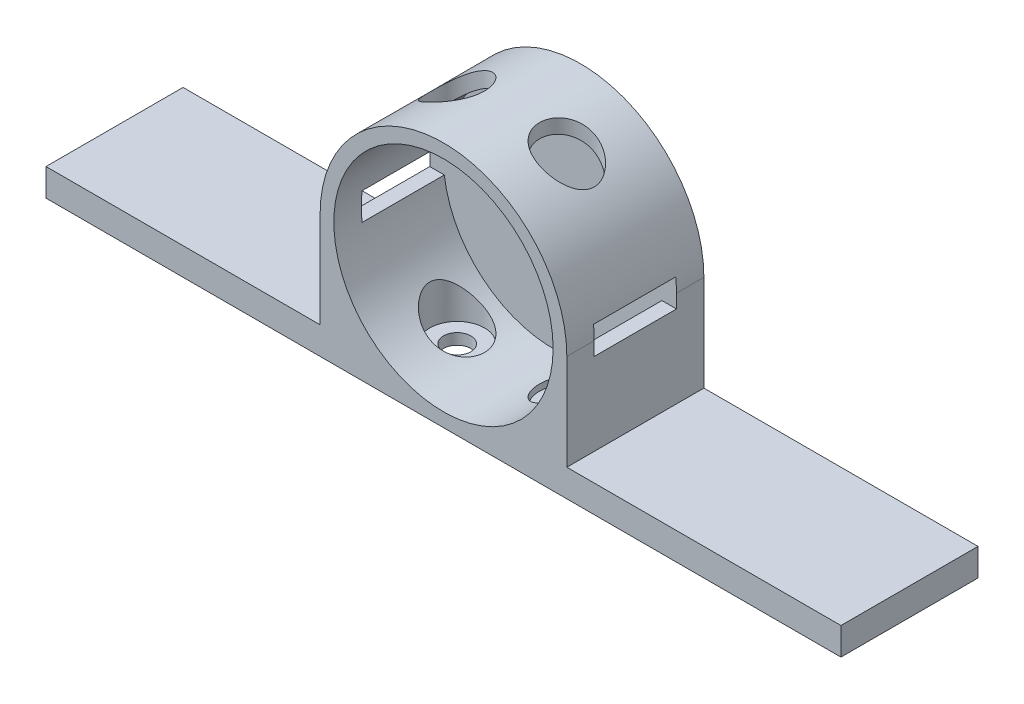
SolidWorks part; units mm, degrees
ref_plane "Front Plane" through (0, 0, 0) normal (0, 0, 1) x (1, 0, 0)
ref_plane "Top Plane" through (0, 0, 0) normal (0, 1, 0) x (1, 0, 0)
ref_plane "Right Plane" through (0, 0, 0) normal (1, 0, 0) x (0, 0, -1)
sketch "Sketch2" plane through (0, 0, 0) normal (0, 0, 1) x (1, 0, 0)
  circle A1 centre (0, 0) radius 22.5
  dimension "D2" = 45
extrude "Boss-Extrude3" add sketch "Sketch2" along normal blind 25
sketch "Sketch6" plane through (0, 0, 0) normal (0, 0, 1) x (1, 0, 0)
  line L1 (-22.5, 0) -> (22.5, 0)
  line L2 (-22.5, 0) -> (-22.5, -22.5)
  line L3 (-22.5, -22.5) -> (22.5, -22.5)
  line L4 (22.5, 0) -> (22.5, -22.5)
  circle A0 centre (0, 0) radius 22.5 construction
extrude "Boss-Extrude4" add sketch "Sketch6" along normal blind 25
sketch "Sketch4" plane through (0, 0, 25) normal (0, 0, 1) x (1, 0, 0)
  circle A0 centre (0, 0) radius 20
  dimension "D1" = 40
extrude "Cut-Extrude1" cut sketch "Sketch4" against normal blind 20
sketch "Sketch5" plane through (0, 0, 0) normal (0, 0, -1) x (-1, 0, 0)
  circle A0 centre (0, 0) radius 2.5
  dimension "D1" = 5
extrude "Cut-Extrude2" cut sketch "Sketch5" against normal up to surface (5 mm away) up to face at (20, 0, 5)
sketch "Sketch7" plane through (0, -22.5, 0) normal (0, -1, 0) x (1, 0, 0)
  line L0 (0, 25) -> (0, 0) construction
  line L1 (-22.5, 25) -> (22.5, 25) construction
  circle A3 centre (-10, 12.5) radius 5
  circle A4 centre (10, 12.5) radius 5
  point P9 (0, 12.5)
  dimension "D2" = 10
  dimension "D4" = 10
extrude "Cut-Extrude6" cut sketch "Sketch7" against normal through all
sketch "Sketch9" plane through (0, -22.5, 0) normal (0, -1, 0) x (1, 0, 0)
  line L0 (0, 25) -> (0, 0) construction
  line L1 (-22.5, 25) -> (22.5, 25) construction
  circle A0 centre (-10, 12.5) radius 5
  circle A1 centre (-10, 12.5) radius 2.5
  circle A2 centre (10, 12.5) radius 2.5
  circle A3 centre (10, 12.5) radius 5
  dimension "D1" = 10
  dimension "D2" = 5
extrude "Boss-Extrude5" add sketch "Sketch9" against normal blind 2
sketch "Sketch14" plane through (22.5, 0, 0) normal (1, 0, 0) x (0, 0, -1)
  line L0 (-25, 0) -> (0, 0) construction
  line L1 (-20, 0) -> (-5, 0)
  line L2 (-20, 2.5) -> (-20, -2.5)
  line L3 (-20, -2.5) -> (-5, -2.5)
  line L4 (-5, 2.5) -> (-5, -2.5)
  line L5 (0, -22.5) -> (0, 0) construction
  line L6 (-25, -22.5) -> (-25, 0) construction
  line L7 (-20, 2.5) -> (-5, 2.5)
  dimension "D1" = 5
  dimension "D2" = 5
  dimension "D3" = 2.5
extrude "Cut-Extrude8" cut sketch "Sketch14" against normal through all contours L7 L4 L3 L2
sketch "Sketch15" plane through (-22.5, 0, 0) normal (-1, 0, 0) x (0, 0, 1)
  line L0 (25, 0) -> (25, -22.5) construction
  line L1 (0, -22.5) -> (25, -22.5)
  line L2 (0, -22.5) -> (0, -17.5)
  line L3 (0, -17.5) -> (25, -17.5)
  line L4 (25, -22.5) -> (25, -17.5)
  dimension "D1" = 5
extrude "Boss-Extrude6" add sketch "Sketch15" along normal blind 50
sketch "Sketch16" plane through (22.5, 0, 0) normal (1, 0, 0) x (0, 0, -1)
  line L0 (0, -22.5) -> (0, 0) construction
  line L1 (-25, -22.5) -> (0, -22.5)
  line L2 (-25, -22.5) -> (-25, -17.5)
  line L3 (-25, -17.5) -> (0, -17.5)
  line L4 (0, -22.5) -> (0, -17.5)
  dimension "D1" = 5
extrude "Boss-Extrude7" add sketch "Sketch16" along normal blind 50
